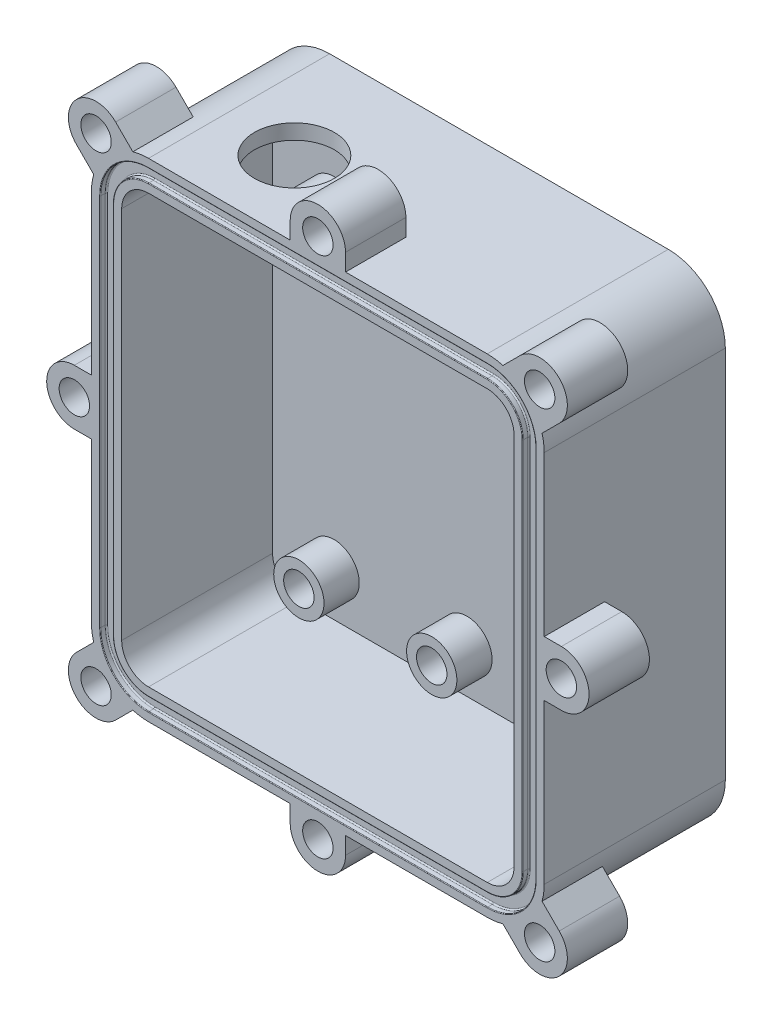
SolidWorks part; units mm, degrees
material "ABS"
ref_plane "X-Y Datum" through (0, 0, 0) normal (0, 0, 1) x (1, 0, 0)
ref_plane "X-Z Datum" through (0, 0, 0) normal (0, 1, 0) x (1, 0, 0)
ref_plane "Y-Z Datum" through (0, 0, 0) normal (1, 0, 0) x (0, 0, -1)
sketch "Sketch2" plane through (0, 0, 0) normal (0, 0, 1) x (1, 0, 0)
  line L5 (34.014, 67.818) -> (84.074, 67.818) construction
  line L6 (34.014, 67.818) -> (34.014, 124.878) construction
  line L7 (34.014, 124.878) -> (84.074, 124.878) construction
  line L8 (84.074, 67.818) -> (84.074, 124.878) construction
  line L9 (34.014, 67.818) -> (84.074, 124.878) construction
  line L10 (34.014, 124.878) -> (84.074, 67.818) construction
  line L14 (20.044, 138.848) -> (98.044, 138.848) construction
  line L15 (98.044, 53.848) -> (98.044, 138.848) construction
  line L16 (20.044, 53.848) -> (98.044, 53.848) construction
  line L17 (20.044, 53.848) -> (20.044, 138.848) construction
  line L18 (25.378, 138.848) -> (92.71, 138.848)
  line L19 (98.044, 59.182) -> (98.044, 133.514)
  line L20 (25.378, 53.848) -> (92.71, 53.848)
  line L21 (20.044, 59.182) -> (20.044, 133.514)
  line L22 (34.014, 96.348) -> (12.446, 96.348) construction
  line L23 (59.044, 67.818) -> (59.044, 60.198) construction
  line L24 (84.074, 96.348) -> (91.694, 96.348) construction
  line L25 (59.044, 124.878) -> (59.044, 132.498) construction
  line L26 (34.014, 124.878) -> (28.6258, 130.2662) construction
  circle A0 centre (25.292, 135.128) radius 2.1 construction
  circle A1 centre (51.708, 135.128) radius 2.1 construction
  circle A2 centre (79.14, 135.128) radius 2.1 construction
  circle A3 centre (51.708, 72.644) radius 2.1 construction
  circle A4 centre (79.14, 72.644) radius 2.1 construction
  circle A5 centre (25.292, 72.644) radius 2.1 construction
  arc A10 (92.71, 138.848) -> (98.044, 133.514) centre (92.71, 133.514) cw
  arc A11 (98.044, 59.182) -> (92.71, 53.848) centre (92.71, 59.182) cw
  arc A12 (25.378, 53.848) -> (20.044, 59.182) centre (25.378, 59.182) cw
  arc A13 (25.378, 138.848) -> (20.044, 133.514) centre (25.378, 133.514) ccw
  point P18 (59.044, 96.348)
  point P32 (20.066, 139.954)
  dimension "D2" = 85
  dimension "D1" = 5.334
  dimension "D4" = 78
  dimension "D3" = 13.97
extrude "Boss-Extrude1" add sketch "Sketch2" along normal blind 30
shell "Shell1" thickness 6
ref_plane "Plane1" through (59.044, 0, 0) normal (1, 0, 0) x (0, 0, -1)
ref_plane "Plane2" through (0, 96.348, 0) normal (0, -1, 0) x (-1, 0, 0)
sketch "Sketch15" plane through (0, 0, 30) normal (0, 0, 1) x (1, 0, 0)
  line L21 (92.71, 143.1307) -> (25.378, 143.1307)
  line L22 (15.7613, 133.514) -> (15.7613, 59.182)
  line L23 (25.378, 49.5653) -> (92.71, 49.5653)
  line L24 (102.3267, 59.182) -> (102.3267, 133.514)
  line L25 (92.71, 141.848) -> (25.378, 141.848)
  line L26 (17.044, 133.514) -> (17.044, 59.182)
  line L27 (25.378, 50.848) -> (92.71, 50.848)
  line L28 (101.044, 59.182) -> (101.044, 133.514)
  line L29 (92.71, 141.848) -> (25.378, 141.848) construction
  line L30 (17.044, 133.514) -> (17.044, 59.182) construction
  line L31 (25.378, 50.848) -> (92.71, 50.848) construction
  line L32 (101.044, 59.182) -> (101.044, 133.514) construction
  line L33 (18.3267, 133.514) -> (18.3267, 59.182)
  line L34 (25.378, 52.1307) -> (92.71, 52.1307)
  line L35 (99.7613, 59.182) -> (99.7613, 133.514)
  line L36 (92.71, 140.5653) -> (25.378, 140.5653)
  arc A17 (25.378, 143.1307) -> (15.7613, 133.514) centre (25.378, 133.514) ccw
  arc A18 (15.7613, 59.182) -> (25.378, 49.5653) centre (25.378, 59.182) ccw
  arc A19 (92.71, 49.5653) -> (102.3267, 59.182) centre (92.71, 59.182) ccw
  arc A20 (102.3267, 133.514) -> (92.71, 143.1307) centre (92.71, 133.514) ccw
  arc A21 (101.044, 133.514) -> (92.71, 141.848) centre (92.71, 133.514) ccw
  arc A22 (25.378, 141.848) -> (17.044, 133.514) centre (25.378, 133.514) ccw
  arc A23 (17.044, 59.182) -> (25.378, 50.848) centre (25.378, 59.182) ccw
  arc A24 (92.71, 50.848) -> (101.044, 59.182) centre (92.71, 59.182) ccw
  arc A25 (101.044, 133.514) -> (92.71, 141.848) centre (92.71, 133.514) ccw construction
  arc A26 (25.378, 141.848) -> (17.044, 133.514) centre (25.378, 133.514) ccw construction
  arc A27 (17.044, 59.182) -> (25.378, 50.848) centre (25.378, 59.182) ccw construction
  arc A28 (92.71, 50.848) -> (101.044, 59.182) centre (92.71, 59.182) ccw construction
  arc A29 (18.3267, 59.182) -> (25.378, 52.1307) centre (25.378, 59.182) ccw
  arc A30 (92.71, 52.1307) -> (99.7613, 59.182) centre (92.71, 59.182) ccw
  arc A31 (99.7613, 133.514) -> (92.71, 140.5653) centre (92.71, 133.514) ccw
  arc A32 (25.378, 140.5653) -> (18.3267, 133.514) centre (25.378, 133.514) ccw
  dimension "D4" = 7.0513
  dimension "D5" = 2.5654
  dimension "D1" = 3
  dimension "D2" = 1.2827
  dimension "D3" = 1.2827
extrude "Cut-Extrude4" cut sketch "Sketch15" against normal blind 1.2446
fillet "Fillet1" radius 0.254 16 edges at (97.696, 54.196, 28.7554) (59.044, 52.1307, 28.7554) (20.392, 54.196, 28.7554) (18.3267, 96.348, 28.7554) (20.392, 138.5, 28.7554) (59.044, 140.5653, 28.7554) (97.696, 138.5, 28.7554) (99.51, 52.382, 28.7554) (59.044, 49.5653, 28.7554) (18.578, 52.382, 28.7554) (15.7613, 96.348, 28.7554) (18.578, 140.314, 28.7554) (59.044, 143.1307, 28.7554) (99.51, 140.314, 28.7554) (99.7613, 96.348, 28.7554) (102.3267, 96.348, 28.7554)
fillet "Fillet2" radius 0.127 16 edges at (99.51, 52.382, 30) (59.044, 49.5653, 30) (18.578, 52.382, 30) (15.7613, 96.348, 30) (18.578, 140.314, 30) (59.044, 143.1307, 30) (99.51, 140.314, 30) (97.696, 54.196, 30) (59.044, 52.1307, 30) (20.392, 54.196, 30) (18.3267, 96.348, 30) (20.392, 138.5, 30) (59.044, 140.5653, 30) (97.696, 138.5, 30) (102.3267, 96.348, 30) (99.7613, 96.348, 30)
sketch "Sketch16" plane through (0, 0, 30) normal (0, 0, 1) x (1, 0, 0)
  line L0 (92.71, 59.182) -> (107.7852, 44.1068) construction
  line L1 (99.2463, 44.8675) -> (95.8284, 48.2854)
  line L2 (107.0245, 52.6457) -> (103.6066, 56.0636)
  arc A0 (92.71, 49.4383) -> (102.4537, 59.182) centre (92.71, 59.182) ccw construction
  circle A1 centre (103.1354, 48.7566) radius 3.025
  circle A2 centre (103.1354, 48.7566) radius 5.5
  arc A3 (92.71, 49.4383) -> (102.4537, 59.182) centre (92.71, 59.182) ccw
  arc A4 (92.71, 47.848) -> (104.044, 59.182) centre (92.71, 59.182) ccw construction
  point P3 (99.5998, 52.2922)
  dimension "D2" = 11
  dimension "D3" = 6.05
  dimension "D1" = 5
extrude "Boss-Extrude7" add sketch "Sketch16" against normal blind 12
sketch "Sketch17" plane through (0, 0, 30) normal (0, 0, 1) x (1, 0, 0)
  circle A0 centre (103.1354, 48.7566) radius 3.025 construction
  circle A1 centre (103.1354, 48.7566) radius 3.025
  dimension "D1" = 6.05
extrude "Cut-Extrude5" cut sketch "Sketch17" against normal blind 9
mirror "Mirror2" about plane through (0, 96.348, 0) normal (0, -1, 0) of "Cut-Extrude5", "Boss-Extrude7"
mirror "Mirror3" about plane through (59.044, 0, 0) normal (1, 0, 0) of "Mirror2", "Cut-Extrude5", "Boss-Extrude7"
sketch "Sketch18" plane through (0, 0, 30) normal (0, 0, 1) x (1, 0, 0)
  line L0 (92.71, 49.4383) -> (25.378, 49.4383) construction
  line L2 (92.71, 49.4383) -> (25.378, 49.4383)
  line L3 (59.044, 49.4383) -> (59.044, 35.8526) construction
  line L4 (53.544, 44.4383) -> (53.544, 47.848)
  line L5 (25.378, 47.848) -> (92.71, 47.848) construction
  line L6 (64.544, 44.4383) -> (64.544, 47.848)
  circle A0 centre (59.044, 44.4383) radius 3.025
  circle A1 centre (59.044, 44.4383) radius 5.5
  dimension "D1" = 6.05
  dimension "D3" = 11
  dimension "D2" = 5
extrude "Boss-Extrude8" add sketch "Sketch18" against normal blind 12
sketch "Sketch19" plane through (0, 0, 30) normal (0, 0, 1) x (1, 0, 0)
  circle A0 centre (59.044, 44.4383) radius 3.025 construction
  circle A1 centre (59.044, 44.4383) radius 3.025
  dimension "D1" = 6.05
extrude "Cut-Extrude6" cut sketch "Sketch19" against normal blind 9
mirror "Mirror4" about plane through (0, 96.348, 0) normal (0, -1, 0) of "Cut-Extrude6", "Boss-Extrude8"
sketch "Sketch20" plane through (0, 0, 30) normal (0, 0, 1) x (1, 0, 0)
  line L0 (102.4537, 133.514) -> (102.4537, 59.182) construction
  line L1 (102.4537, 133.514) -> (102.4537, 59.182)
  line L2 (102.4537, 96.348) -> (119.767, 96.348) construction
  line L3 (107.4537, 90.848) -> (104.044, 90.848)
  line L4 (104.044, 59.182) -> (104.044, 133.514) construction
  line L5 (107.4537, 101.848) -> (104.044, 101.848)
  circle A0 centre (107.4537, 96.348) radius 3.025
  circle A1 centre (107.4537, 96.348) radius 5.5
  dimension "D1" = 6.05
  dimension "D2" = 11
  dimension "D3" = 5
extrude "Boss-Extrude9" add sketch "Sketch20" against normal blind 12
mirror "Mirror5" about plane through (59.044, 0, 0) normal (1, 0, 0) of "Boss-Extrude9"
sketch "Sketch22" plane through (14.044, 0, 0) normal (-1, 0, 0) x (0, 0, 1)
  line L0 (30, 96.348) -> (-6, 96.348) construction
  line L1 (30, 90.848) -> (30, 101.848) construction
  line L2 (-6, 133.514) -> (-6, 59.182) construction
  line L3 (9, 133.514) -> (9, 59.182) construction
  line L4 (-1, 126.348) -> (19, 126.348)
  line L5 (-1, 126.348) -> (-1, 66.348)
  line L6 (-1, 66.348) -> (19, 66.348)
  line L7 (19, 126.348) -> (19, 66.348)
  line L8 (-1, 126.348) -> (19, 66.348) construction
  line L9 (-1, 66.348) -> (19, 126.348) construction
  point P22 (9, 96.348)
  dimension "D1" = 60
  dimension "D2" = 20
  dimension "D3" = 5
extrude "Boss-Extrude10" [suppressed] add sketch "Sketch22" along normal blind 12
sketch "Sketch23" [suppressed] plane through (2.044, 0, 0) normal (-1, 0, 0) x (0, 0, 1)
  line L0 (19, 96.348) -> (-1, 96.348) construction
  line L1 (19, 66.348) -> (19, 126.348) construction
  line L2 (-1, 126.348) -> (-1, 66.348) construction
  line L3 (9, 66.348) -> (9, 126.348) construction
  line L4 (-1, 66.348) -> (19, 66.348) construction
  line L5 (19, 126.348) -> (-1, 126.348) construction
  circle A0 centre (9, 76.028) radius 3.025
  circle A1 centre (9, 116.668) radius 3.025
  dimension "D2" = 6.05
  dimension "D1" = 20.32
extrude "Cut-Extrude8" [suppressed] cut sketch "Sketch23" against normal blind 8
sketch "Sketch21" plane through (0, 0, 30) normal (0, 0, 1) x (1, 0, 0)
  circle A2 centre (10.6343, 96.348) radius 3.025
  dimension "D1" = 6.05
extrude "Cut-Extrude9" cut sketch "Sketch21" against normal blind 9
sketch "Sketch24" plane through (0, 47.848, 0) normal (0, -1, 0) x (1, 0, 0)
  line L0 (92.71, 30) -> (92.71, -6) construction
  line L1 (25.378, 30) -> (92.71, 30)
  line L2 (25.378, 30) -> (25.378, 18)
  line L3 (25.378, 18) -> (92.71, 18)
  line L4 (92.71, 30) -> (92.71, 18)
  dimension "D1" = 12
extrude "Boss-Extrude11" [suppressed] add sketch "Sketch24" along normal blind 16
sketch "Sketch25" plane through (0, 0, 30) normal (0, 0, 1) x (1, 0, 0)
  line L0 (-12.3805, 96.348) -> (12.3805, 96.348) construction
  circle A0 centre (59.044, 44.4383) radius 3.025
  circle A1 centre (59.044, 148.2577) radius 3.025
  circle A2 centre (59.044, 148.2577) radius 3.025
  dimension "D1" = 0
extrude "Cut-Extrude10" [suppressed] cut sketch "Sketch25" against normal blind 9 contours A0
sketch "Sketch26" [suppressed] plane through (0, 0, 30) normal (0, 0, 1) x (1, 0, 0)
  line L0 (25.378, 39.848) -> (92.71, 39.848) construction
  line L1 (25.378, 47.848) -> (92.71, 47.848)
  line L2 (25.378, 47.848) -> (25.378, 31.848)
  line L3 (25.378, 31.848) -> (92.71, 31.848)
  line L4 (92.71, 47.848) -> (92.71, 31.848)
  line L5 (59.044, 31.848) -> (59.044, 47.848) construction
  line L6 (25.378, 47.848) -> (59.044, 47.848)
  line L7 (59.044, 47.848) -> (42.211, 47.848)
  line L8 (42.211, 47.848) -> (42.211, 31.848) construction
  circle A2 centre (42.211, 39.848) radius 3.025
  circle A4 centre (75.877, 39.848) radius 3.025
  dimension "D1" = 6.05
extrude "Cut-Extrude11" [suppressed] cut sketch "Sketch26" against normal blind 9
mirror "Mirror6" [suppressed] about plane through (59.044, 0, 0) normal (1, 0, 0)
mirror "Mirror7" [suppressed] about plane through (59.044, 0, 0) normal (1, 0, 0)
fillet "Fillet3" [suppressed] radius 2
sketch "Sketch27" plane through (0, 144.848, 0) normal (0, 1, 0) x (1, 0, 0)
  line L0 (25.378, -12) -> (92.71, -12) construction
  line L1 (25.378, -30) -> (25.378, 6) construction
  line L2 (92.71, -30) -> (92.71, 6) construction
  line L3 (92.71, -30) -> (64.544, -30) construction
  circle A1 centre (39.378, -15) radius 7.9375
  circle A2 centre (39.378, -15) radius 12.7
  dimension "D1" = 15.875
  dimension "D3" = 25.4
  dimension "D2" = 15
  dimension "D4" = 14
extrude "Cut-Extrude12" cut sketch "Sketch27" against normal blind 6 contours L0 A1 | A1 L0
sketch "Sketch28" plane through (0, 0, 0) normal (0, 0, 1) x (1, 0, 0)
  circle A0 centre (32.266, 125.158) radius 3.025
  circle A1 centre (58.682, 125.158) radius 3.025
  circle A2 centre (86.114, 125.158) radius 3.025
  circle A3 centre (32.266, 62.674) radius 3.025
  circle A4 centre (58.682, 62.674) radius 3.025
  circle A5 centre (86.114, 62.674) radius 3.025
  circle A6 centre (32.266, 125.158) radius 5
  circle A7 centre (58.682, 125.158) radius 5
  circle A8 centre (86.114, 125.158) radius 5
  circle A9 centre (32.266, 62.674) radius 5
  circle A10 centre (58.682, 62.674) radius 5
  circle A11 centre (86.114, 62.674) radius 5
  point P0 (32.266, 125.158)
  point P1 (58.682, 125.158)
  point P3 (86.114, 125.158)
  point P5 (32.266, 62.674)
  point P7 (58.682, 62.674)
  point P9 (86.114, 62.674)
  dimension "D1" = 6.05
  dimension "D2" = 10
extrude "Boss-Extrude12" add sketch "Sketch28" along normal blind 7
sketch "Sketch29" plane through (0, 138.848, 0) normal (0, -1, 0) x (1, 0, 0)
  circle A0 centre (39.378, 15) radius 12.7 construction
  circle A1 centre (39.378, 15) radius 12.7
extrude "Cut-Extrude13" cut sketch "Sketch29" against normal blind 3
sketch "Sketch30" plane through (0, 0, 30) normal (0, 0, 1) x (1, 0, 0)
  circle A0 centre (107.4537, 96.348) radius 3.025 construction
  circle A1 centre (107.4537, 96.348) radius 3.025
extrude "Cut-Extrude14" cut sketch "Sketch30" against normal blind 9
